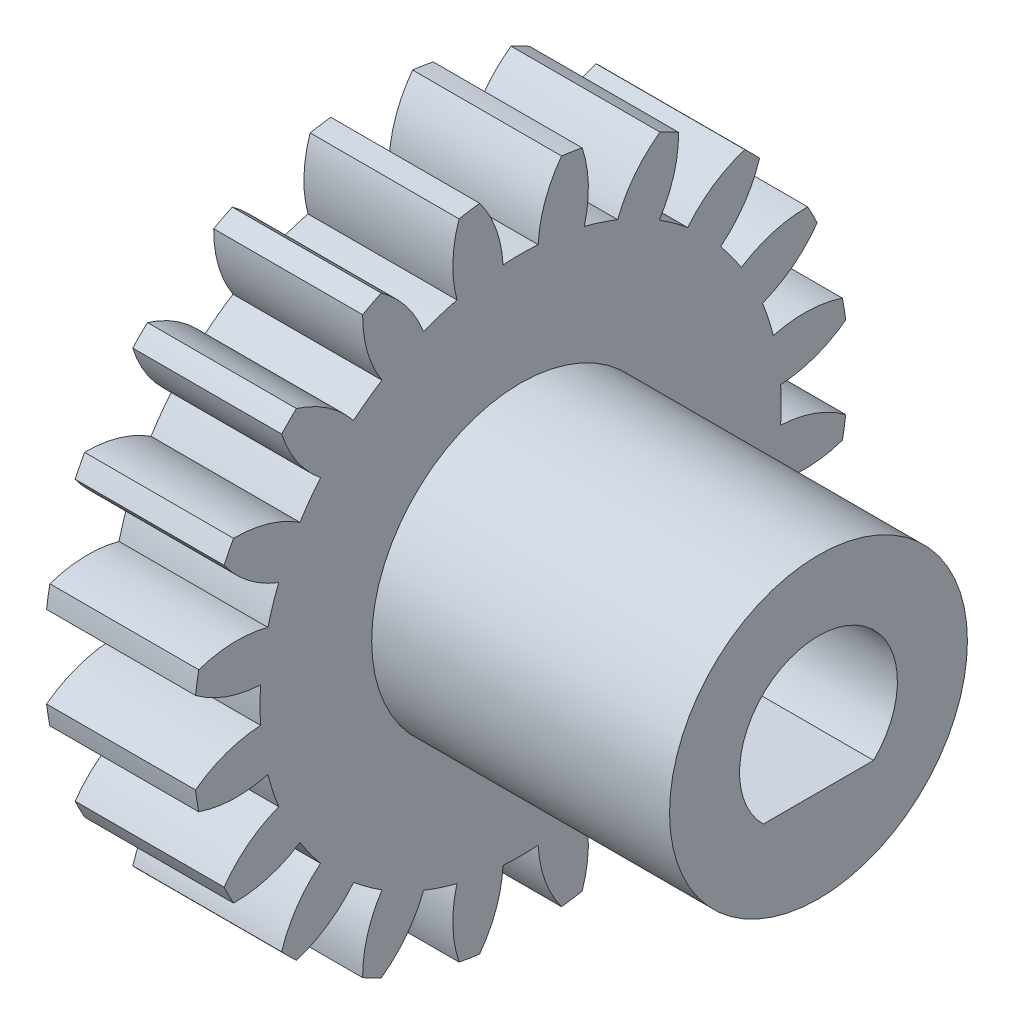
SolidWorks part; units mm, degrees
ref_plane "Plane1" through (0, 0, 0) normal (0, 0, 1) x (1, 0, 0)
ref_plane "Plane2" through (0, 0, 0) normal (0, 1, 0) x (1, 0, 0)
ref_plane "Plane3" through (0, 0, 0) normal (1, 0, 0) x (0, 0, -1)
sketch "HoldingSke" plane through (0, 0, 0) normal (0, 1, 0) x (1, 0, 0)
  line L0 (0, 0) -> (0.9397, -0.342)
  line L1 (-15, 0) -> (100, 0) construction
  line L2 (0, 0) -> (-2.1039, 2.3779)
  line L3 (0, 0) -> (-11.863, 4.5341)
  line L4 (0, 0) -> (8.1152, 2.9537)
  line L5 (0, 0) -> (-46.8476, -17.4728)
  line L6 (0, 0) -> (-4.1448, -2.7965)
  line L7 (-2.1039, 2.3779) -> (8.6586, 51.2059)
  line L8 (-76.2, 54.61) -> (-75.3, 54.61)
  line L9 (-67.7845, 28.3722) -> (-49.3413, 33.142)
  line L10 (-76.2, 71.12) -> (104.1128, 71.12)
  line L11 (0, 0) -> (-5, 0)
  line L12 (-76.2, 101.6) -> (-76.162, 101.6)
  line L13 (24.9733, 27.94) -> (52.9518, 28.4284)
  line L14 (24.9733, 27.94) -> (24.9743, 27.94)
  line L15 (24.9733, 27.94) -> (100.4006, 29.5858)
  line L16 (-63.627, -1) -> (-12.827, -1)
  circle A0 centre (0, 0) radius 2.5
  circle A1 centre (0, 0) radius 8.749
  circle A2 centre (0, 0) radius 37.5
  circle A3 centre (0, 0) radius 2.5
  dimension "MHD" = 17.498
  dimension "Hub_dia" = 75
  dimension "Bore" = 5
  dimension "MBD" = 5
  dimension "Num_teeth" = 20
  dimension "Pitch" = 1
  dimension "Overall_len" = 50
  dimension "Show_teeth" = 20
  dimension "Thickness" = 5
  dimension "OAL" = 50.0001
  dimension "T_dim" = 0.9
  dimension "Ap" = 14.5
  dimension "H" = 19.05
  dimension "Pitch_radius" = 180.3128
  dimension "Width" = 5
  dimension "Backlash" = 0.038
  dimension "Addendum_fac" = 1
  dimension "Dedendum_fac" = 1.25
  dimension "Clearance_fac" = 0.25
  dimension "Dedendum_add" = 0.001
  dimension "Module" = 1
sketch "BasProSke" plane through (0, 0, 0) normal (0, 1, 0) x (1, 0, 0)
  line L0 (-10, 0) -> (60, 0) construction
  line L1 (0, 0) -> (0, 11)
  line L2 (0, 0) -> (5, 0)
  line L3 (5, 0) -> (5, 11)
  line L4 (5, 11) -> (0, 11)
  dimension "Thickness" = 5
  dimension "Diameter" = 22
revolve "Base-Revolve" add sketch "BasProSke" angle 360 about L0
sketch "TooCutSke" plane through (0, 0, 0) normal (1, 0, 0) x (0, 0, -1)
  line L1 (0, 0) -> (0, 107) construction
  line L2 (0, 0) -> (-0.8511, 9.9637) construction
  line L3 (0, 0) -> (-3.1206, 19.7028) construction
  line L4 (-0.8511, 9.9637) -> (-1.5603, 9.8514) construction
  arc A0 (0.5894, 8.7291) -> (-0.5894, 8.7291) centre (0, 0) ccw
  arc A1 (1.3917, 10.9372) -> (-1.3917, 10.9372) centre (0, 0) ccw
  circle A2 centre (0, 0) radius 10 construction
  circle A3 centre (0, 0) radius 9.6815 construction
  arc A4 (-0.5894, 8.7291) -> (-1.3917, 10.9372) centre (-4.5843, 8.5273) ccw
  arc A5 (1.3917, 10.9372) -> (0.5894, 8.7291) centre (4.5843, 8.5273) ccw
  dimension "Root_dia" = 17.498
  dimension "Overcut_dia" = 22.0508
  dimension "Pitch_dia" = 20
  dimension "Base_dia" = 19.363
  dimension "Flank_rad" = 4
  dimension "Half_ang" = 9
  dimension "Half_CT" = 0.7181
extrude "ToothCut" cut sketch "TooCutSke" along normal through all
fillet "Breaks" [suppressed] radius 0.02 tangent propagation no
fillet "RootFillets" [suppressed] radius 0.251
pattern_circular "TeethCuts" count 20 every 18 about axis through (-10, 0, 0) along (1, 0, 0) of "ToothCut", "RootFillets", "Breaks"
sketch "HubNeaOneSke" plane through (0, 0, 0) normal (-1, 0, 0) x (0, 0, 1)
  circle A0 centre (0, 0) radius 8.749
  dimension "Diameter" = 17.498
extrude "HubNearOne" [suppressed] add sketch "HubNeaOneSke" along normal blind 45.0001
sketch "HubNeaBotSke" plane through (0, 0, 0) normal (-1, 0, 0) x (0, 0, 1)
  circle A0 centre (0, 0) radius 8.749
  dimension "Diameter" = 17.498
extrude "HubNearBoth" [suppressed] add sketch "HubNeaBotSke" along normal blind 22.5
ref_plane "FarPln" through (5, 0, 0) normal (1, 0, 0) x (0, 0, -1)
sketch "HubFarSke" plane through (5, 0, 0) normal (1, 0, 0) x (0, 0, -1)
  circle A0 centre (0, 0) radius 8.749
  dimension "Diameter" = 17.498
extrude "HubFar" [suppressed] add sketch "HubFarSke" along normal blind 22.5
sketch "BorSke" plane through (0, 0, 0) normal (1, 0, 0) x (0, 0, -1)
  circle A0 centre (0, 0) radius 2.5
  dimension "Diameter" = 5
extrude "Bore" cut sketch "BorSke" along normal mid plane 100.0001
sketch "KeySke" plane through (0, 0, 0) normal (1, 0, 0) x (0, 0, -1)
  line L0 (-1, 0) -> (-1, 3.4)
  line L1 (-1, 3.4) -> (1, 3.4)
  line L2 (1, 3.4) -> (1, 0)
  line L3 (0, 0) -> (0, 34) construction
  line L4 (-1, 0) -> (1, 0)
  dimension "Offset" = 3.4
  dimension "Width" = 2
extrude "Keyway" [suppressed] cut sketch "KeySke" along normal mid plane 100.0001
pattern_circular "Keyway2" [suppressed] count 2 every 90 about axis through (-10, 0, 0) along (1, 0, 0) reverse direction yes
sketch "Sketch1" plane through (5, 0, 0) normal (1, 0, 0) x (0, 0, -1)
  circle A0 centre (0, 0) radius 5
  dimension "D1" = 10
extrude "Boss-Extrude2" add sketch "Sketch1" along normal blind 10 and the other way through all
sketch "Sketch2" plane through (15, 0, 0) normal (1, 0, 0) x (0, 0, -1)
  line L0 (-1.85, -1.8974) -> (1.85, -1.8974)
  circle A0 centre (0, 0) radius 2.65
  dimension "D1" = 5.3
  dimension "D2" = 3.7
extrude "Cut-Extrude1" cut sketch "Sketch2" against normal through all contours L0 A0 region at (15, 0.2095, 0)
equation "' \"Module@HoldingSke\" = 6.35"
equation "' \"Num_teeth@HoldingSke\" = 12"
equation "' \"Ap@HoldingSke\" =  20"
equation "' \"Ap@HoldingSke\" = 20"
equation "' \"Width@HoldingSke\" = 0.5 * 25.4"
equation "' \"Hub_dia@HoldingSke\"= 1 * 25.4"
equation "' \"Hub_dia@HoldingSke\" = 1 * 25.4"
equation "' \"Overall_len@HoldingSke\" = 1.0 * 25.4"
equation "' \"Bore@HoldingSke\" = 0.75 * 25.4"
equation "' \"T_dim@HoldingSke\" = 0.1 * 25.4"
equation "' \"Width@KeySke\" = 0.25 * 25.4"
equation "' \"Show_teeth@HoldingSke\" = 13"
equation "' \"Backlash@HoldingSke\" = 0.009 * 25.4"
equation "' \"Addendum_fac@HoldingSke\" = 1.0"
equation "' \"Dedendum_fac@HoldingSke\" = 1.25"
equation "' \"Dedendum_add@HoldingSke\" = 0.00005 * 25.4"
equation "' \"Clearance_fac@HoldingSke\" = 0.25"
equation "\"Pitch@HoldingSke\" = 1 / \"Module@HoldingSke\""
equation "\"Overcut_dia@TooCutSke\" = (\"Num_teeth@HoldingSke\" + 2 * \"Addendum_fac@HoldingSke\") / \"Pitch@HoldingSke\" + 0.002 * 25.4"
equation "\"Pitch_dia@TooCutSke\" = \"Num_teeth@HoldingSke\" / \"Pitch@HoldingSke\""
equation "\"Base_dia@TooCutSke\" = \"Num_teeth@HoldingSke\" / \"Pitch@HoldingSke\" * cos((\"Ap@HoldingSke\"  * 3.14159265 / 180))"
equation "\"Root_dia@TooCutSke\" = (\"Num_teeth@HoldingSke\" + 2) / \"Pitch@HoldingSke\" - 2 * (\"Addendum_fac@HoldingSke\" + \"Dedendum_fac@HoldingSke\") / \"Pitch@HoldingSke\" - \"Dedendum_add@HoldingSke\" * 2"
equation "\"Half_ang@TooCutSke\" = 180 / \"Num_teeth@HoldingSke\""
equation "\"Half_CT@TooCutSke\" = \"Num_teeth@HoldingSke\" / \"Pitch@HoldingSke\" * sin((3.14159265 / 2 / \"Num_teeth@HoldingSke\")) / 2 - 7 * \"Backlash@HoldingSke\" / 4"
equation "\"Flank_rad@TooCutSke\" = \"Num_teeth@HoldingSke\" / \"Pitch@HoldingSke\" / 5"
equation "\"Radius@RootFillets\" = \"Clearance_fac@HoldingSke\" / \"Pitch@HoldingSke\" + \"Dedendum_add@HoldingSke\""
equation "\"Break_rad@Breaks\" = 0.02 / \"Pitch@HoldingSke\""
equation "\"Thickness@HoldingSke\" = \"Width@HoldingSke\""
equation "\"OAL@HoldingSke\" = \"Thickness@HoldingSke\""
equation "\"MHD@HoldingSke\" = (\"Num_teeth@HoldingSke\" + 2) / \"Pitch@HoldingSke\" - 2 * (\"Addendum_fac@HoldingSke\" + \"Dedendum_fac@HoldingSke\")  / \"Pitch@HoldingSke\" - \"Dedendum_add@HoldingSke\" * 2"
equation "\"MBD@HoldingSke\" = (\"Num_teeth@HoldingSke\" + 2) / \"Pitch@HoldingSke\" - 2 * (\"Addendum_fac@HoldingSke\" + \"Dedendum_fac@HoldingSke\")  / \"Pitch@HoldingSke\" - \"Dedendum_add@HoldingSke\" * 2 - 0.002 * 25.4"
equation "\"MHD@HoldingSke\" = ((sgn( \"MHD@HoldingSke\" - \"Hub_dia@HoldingSke\" )-1)*( \"MHD@HoldingSke\" - \"Hub_dia@HoldingSke\" ))/-2+ \"Hub_dia@HoldingSke\""
equation "\"MBD@HoldingSke\" = ((sgn( \"MBD@HoldingSke\" - \"Bore@HoldingSke\" )-1)*( \"MBD@HoldingSke\" - \"Bore@HoldingSke\" ))/-2+ \"Bore@HoldingSke\""
equation "\"OAL@HoldingSke\" = ((sgn( \"OAL@HoldingSke\" - \"Overall_len@HoldingSke\" )+1)*( \"OAL@HoldingSke\" - \"Overall_len@HoldingSke\" ))/2 + \"Overall_len@HoldingSke\" + 0.000002 * 25.4"
equation "\"Num_teeth@TeethCuts\" = int( \"Show_teeth@HoldingSke\" ) + 1"
equation "\"Num_teeth@TeethCuts\" = ((sgn( \"Num_teeth@TeethCuts\" - \"Num_teeth@HoldingSke\" )-1)*( \"Num_teeth@TeethCuts\" - \"Num_teeth@HoldingSke\" ))/-2+ \"Num_teeth@HoldingSke\""
equation "\"Num_teeth@TeethCuts\" = ((sgn( \"Num_teeth@TeethCuts\" - 2.0)+1)*( \"Num_teeth@TeethCuts\" - 2.0))/2 +2.0"
equation "\"Angle@TeethCuts\" = 360.0 / \"Num_teeth@HoldingSke\""
equation "\"Diameter@BasProSke\" = (\"Num_teeth@HoldingSke\" + 2 * \"Addendum_fac@HoldingSke\") / \"Pitch@HoldingSke\""
equation "\"Thickness@BasProSke\"  = \"Thickness@HoldingSke\""
equation "' \"Fillet_rad@BasProSke\" =  \"Thickness@HoldingSke\" * 0.05"
equation "' \"Fillet_rad@BasProSke\" = \"Thickness@HoldingSke\" * 0.05"
equation "\"MHD@HoldingSke\" = ((sgn( \"MHD@HoldingSke\" - \"Root_dia@TooCutSke\" )-1)*( \"MHD@HoldingSke\" - \"Root_dia@TooCutSke\" ))/-2+ \"Root_dia@TooCutSke\""
equation "\"Diameter@HubNeaOneSke\" = \"MHD@HoldingSke\""
equation "\"Length@HubNearOne\" = \"OAL@HoldingSke\" - \"Thickness@BasProSke\""
equation "\"Diameter@HubNeaBotSke\" = \"MHD@HoldingSke\""
equation "\"Length@HubNearBoth\" = ( \"OAL@HoldingSke\" - \"Thickness@BasProSke\" ) / 2.0"
equation "\"Thickness@FarPln\" = \"Thickness@BasProSke\""
equation "\"Diameter@HubFarSke\" = \"MHD@HoldingSke\""
equation "\"Length@HubFar\" = ( \"OAL@HoldingSke\" - \"Thickness@BasProSke\" ) / 2.0"
equation "\"Diameter@BorSke\" = \"MBD@HoldingSke\""
equation "\"D1@Bore\" = \"OAL@HoldingSke\" * 2.0"
equation "\"D1@Keyway\" = \"OAL@HoldingSke\" * 2.0"
equation "\"Offset@KeySke\" = \"T_dim@HoldingSke\" + \"MBD@HoldingSke\" / 2.0"
